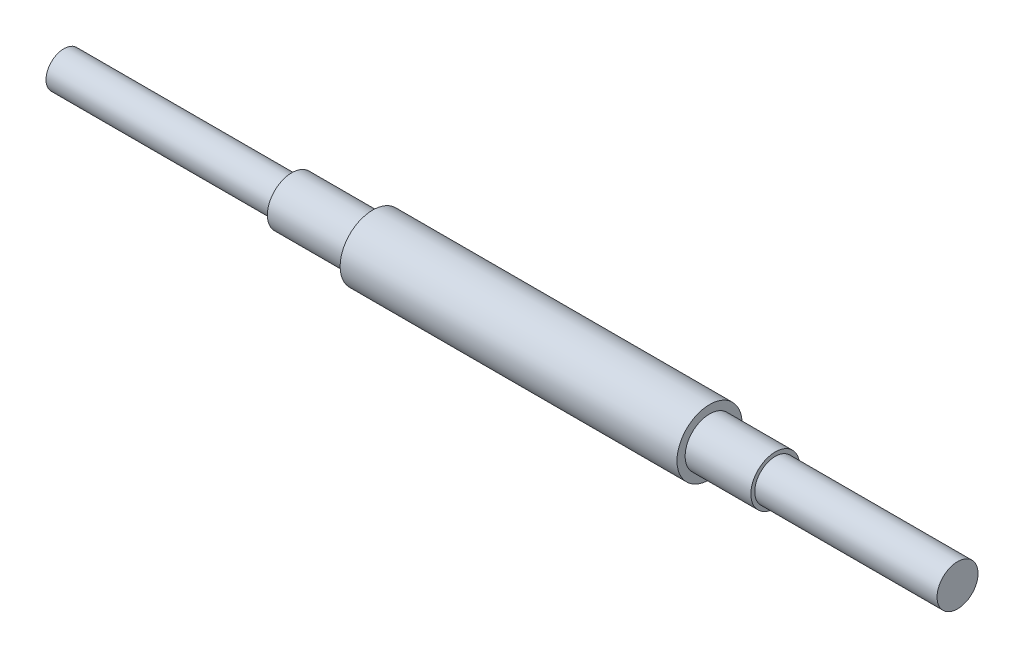
SolidWorks part; units mm, degrees
ref_plane "Front Plane" through (0, 0, 0) normal (0, 0, 1) x (1, 0, 0)
ref_plane "Top Plane" through (0, 0, 0) normal (0, 1, 0) x (1, 0, 0)
ref_plane "Right Plane" through (0, 0, 0) normal (1, 0, 0) x (0, 0, -1)
sketch "Sketch1" plane through (0, 0, 0) normal (0, 1, 0) x (1, 0, 0)
  line L0 (-78.6306, 0) -> (95.703, 0) construction
  line L1 (-78.6306, 0) -> (-78.6306, 3.5)
  line L2 (-78.6306, 3.5) -> (-34.1806, 3.5)
  line L3 (-34.1806, 3.5) -> (-34.1806, 4.7625)
  line L4 (-34.1806, 4.7625) -> (-18.3983, 4.7625)
  line L5 (-18.3983, 4.7625) -> (-18.3983, 6.35)
  line L6 (-18.3983, 6.35) -> (47.3216, 6.35)
  line L7 (47.3216, 6.35) -> (47.3216, 4.7625)
  line L8 (47.3216, 4.7625) -> (60.143, 4.7625)
  line L9 (60.143, 4.7625) -> (60.143, 3.9992)
  line L10 (60.143, 3.9992) -> (95.703, 3.9992)
  line L11 (95.703, 3.9992) -> (95.703, 0)
  line L12 (-78.6306, 0) -> (95.703, 0)
  line L13 (-97.9506, 0) -> (194.5593, 0) construction
  point P15 (0, 0)
  dimension "D1" = 7
  dimension "D2" = 9.525
  dimension "D3" = 9.525
  dimension "D4" = 7.9985
  dimension "D5" = 44.45
  dimension "D6" = 15.7822
  dimension "D7" = 12.8214
  dimension "D8" = 35.56
  dimension "D9" = 65.72
  dimension "D10" = 6.35
revolve "Revolve1" add sketch "Sketch1" angle 360 about L13
